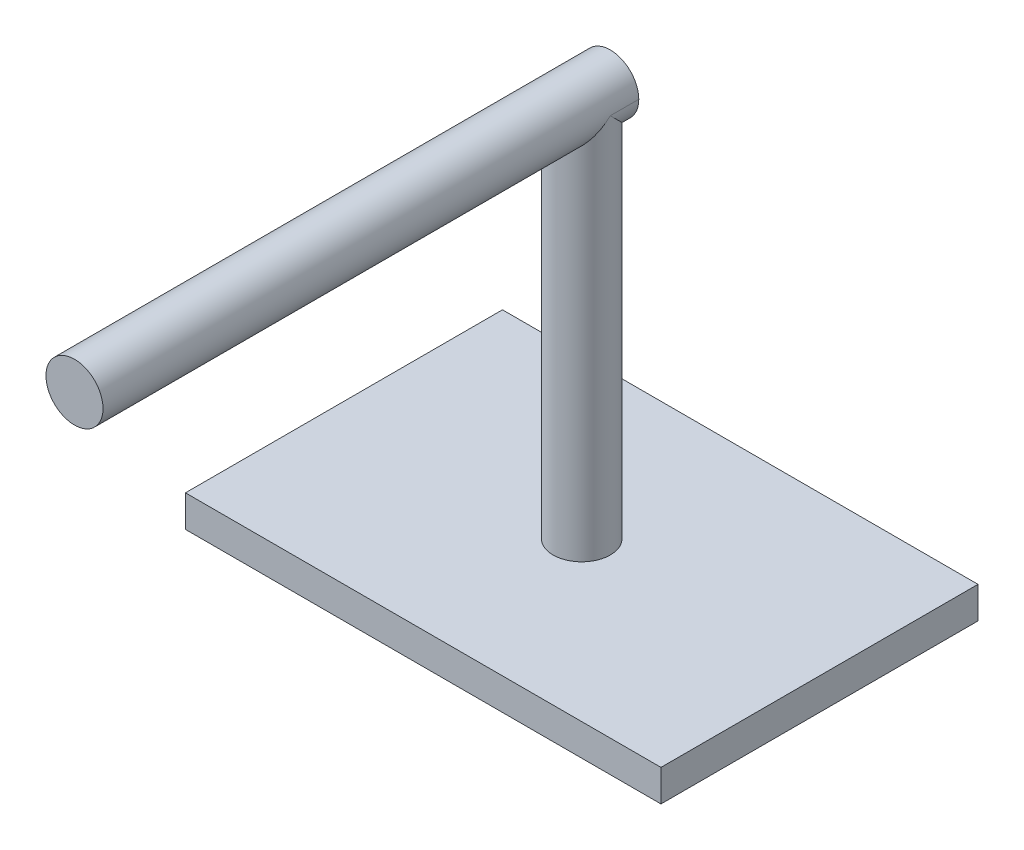
SolidWorks part; units mm, degrees
ref_plane "Front Plane" through (0, 0, 0) normal (0, 0, 1) x (1, 0, 0)
ref_plane "Top Plane" through (0, 0, 0) normal (0, 1, 0) x (1, 0, 0)
ref_plane "Right Plane" through (0, 0, 0) normal (1, 0, 0) x (0, 0, -1)
sketch "Sketch1" plane through (0, 0, 0) normal (0, 1, 0) x (1, 0, 0)
  line L1 (-75, 50) -> (75, 50)
  line L2 (-75, 50) -> (-75, -50)
  line L3 (-75, -50) -> (75, -50)
  line L4 (75, 50) -> (75, -50)
  line L5 (-75, 50) -> (75, -50) construction
  line L6 (-75, -50) -> (75, 50) construction
  point P0 (0, 0)
  dimension "D1" = 100
  dimension "D2" = 150
extrude "Boss-Extrude1" add sketch "Sketch1" along normal blind 10
sketch "Sketch2" plane through (0, 10, 0) normal (0, 1, 0) x (1, 0, 0)
  circle A0 centre (0, 0) radius 11
  dimension "D1" = 22
ref_plane "Plane1" through (0, 0, 40) normal (0, 0, 1) x (1, 0, 0)
sketch "Sketch6" plane through (0, 10, 0) normal (0, 1, 0) x (1, 0, 0)
  circle A1 centre (0, 0) radius 9
  dimension "D1" = 18
extrude "Boss-Extrude6" add sketch "Sketch6" along normal blind 120
sketch "Sketch7" plane through (0, 0, 40) normal (0, 0, 1) x (1, 0, 0)
  line L0 (9, 130) -> (-9, 130) construction
  circle A0 centre (0, 130) radius 9
  dimension "D1" = 18
extrude "Boss-Extrude7" add sketch "Sketch7" along normal blind 120 and the other way blind 49
